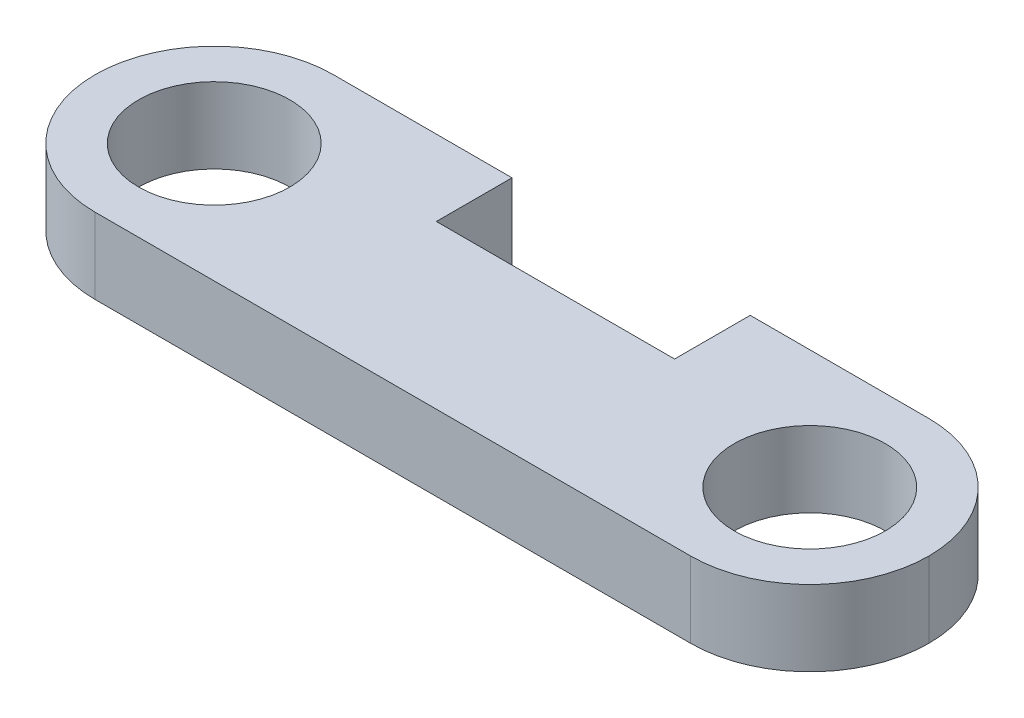
SolidWorks part; units mm, degrees
material "ABS"
ref_plane "Front Plane" through (0, 0, 0) normal (0, 0, 1) x (1, 0, 0)
ref_plane "Top Plane" through (0, 0, 0) normal (0, 1, 0) x (1, 0, 0)
ref_plane "Right Plane" through (0, 0, 0) normal (1, 0, 0) x (0, 0, -1)
sketch "Sketch1" plane through (0, 0, 0) normal (0, 1, 0) x (1, 0, 0)
  line L1 (-35, 10) -> (35, 10)
  line L2 (-35, 10) -> (-35, -10)
  line L3 (-35, -10) -> (35, -10)
  line L4 (35, 10) -> (35, -10)
  point P5 (0, 10)
  point P7 (-35, 0)
  dimension "D1" = 20
  dimension "D2" = 70
extrude "Boss-Extrude1" add sketch "Sketch1" along normal blind 6.35
sketch "Sketch2" plane through (0, 6.35, 0) normal (0, 1, 0) x (1, 0, 0)
  circle A0 centre (-25, 0) radius 6.35
  circle A1 centre (25, 0) radius 6.35
  dimension "D1" = 12.7
  dimension "D2" = 50
  dimension "D3" = 25
extrude "Cut-Extrude1" cut sketch "Sketch2" against normal up to surface (6.35 mm away) up to face at (0, 0, 0)
fillet "Congé1" radius 10 4 edges at (35, 3.175, 10) (35, 3.175, -10) (-35, 3.175, 10) (-35, 3.175, -10)
sketch "Esquisse1" plane through (0, 0, 0) normal (0, -1, 0) x (1, 0, 0)
  line L0 (25, -10) -> (-25, -10) construction
  line L1 (-10, -10) -> (10, -10)
  line L2 (-10, -10) -> (-10, -3.65)
  line L3 (-10, -3.65) -> (10, -3.65)
  line L4 (10, -10) -> (10, -3.65)
  point P6 (0, -3.65)
  dimension "D1" = 6.35
  dimension "D2" = 20
  dimension "D3" = 0
extrude "Enlèv. mat.-Extru.1" cut sketch "Esquisse1" against normal up to surface (6.35 mm away) up to face at (-25, 6.35, 6.35)
